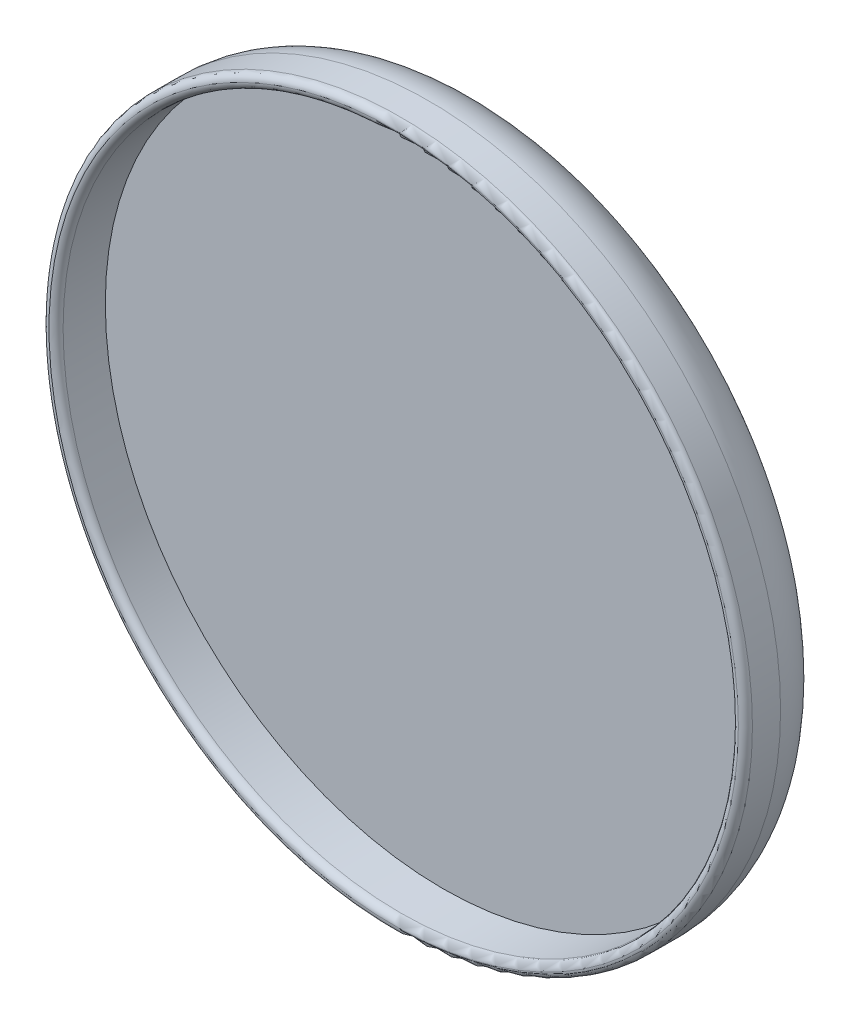
SolidWorks part; units mm, degrees
ref_plane "Front Plane" through (0, 0, 0) normal (0, 0, 1) x (1, 0, 0)
ref_plane "Top Plane" through (0, 0, 0) normal (0, 1, 0) x (1, 0, 0)
ref_plane "Right Plane" through (0, 0, 0) normal (1, 0, 0) x (0, 0, -1)
sketch "Sketch1" plane through (0, 0, 0) normal (0, 0, 1) x (1, 0, 0)
  circle A0 centre (0, 0) radius 1.95
extrude "Boss-Extrude1" add sketch "Sketch1" along normal blind 3.75 and the other way blind 3.5
sketch "Sketch2" plane through (0, 0, 3.75) normal (0, 0, 1) x (1, 0, 0)
  circle A0 centre (0, 14.7501) radius 25
  point P2 (0, 2.9474)
  point P3 (0, 2.243)
  point P4 (0, 0)
  point P6 (0, 0)
  point P7 (0, 16.8567)
  point P8 (0, 14.7501)
  dimension "D1" = 50
extrude "Boss-Extrude2" add sketch "Sketch2" along normal blind 3
sketch "Sketch3" plane through (0, 0, 6.75) normal (0, 0, 1) x (1, 0, 0)
  circle A0 centre (0, 14.7501) radius 25
  circle A1 centre (0, 14.7501) radius 25 construction
  circle A2 centre (0, 14.7501) radius 24
extrude "Boss-Extrude3" add sketch "Sketch3" along normal blind 3.5
fillet "Fillet1" radius 0.5 2 edges at (25, 14.7501, 10.25) (24, 14.7501, 10.25)
fillet "Fillet2" radius 4 1 edges at (25, 14.7501, 3.75)
chamfer "Chamfer1" distance 3 angle 48 1 edges at (1.95, 0, 3.75) first distance on face at (1.95, 0, -3.5)
fillet "Fillet3" radius 1 1 edges at (1.95, 0, -3.5)
